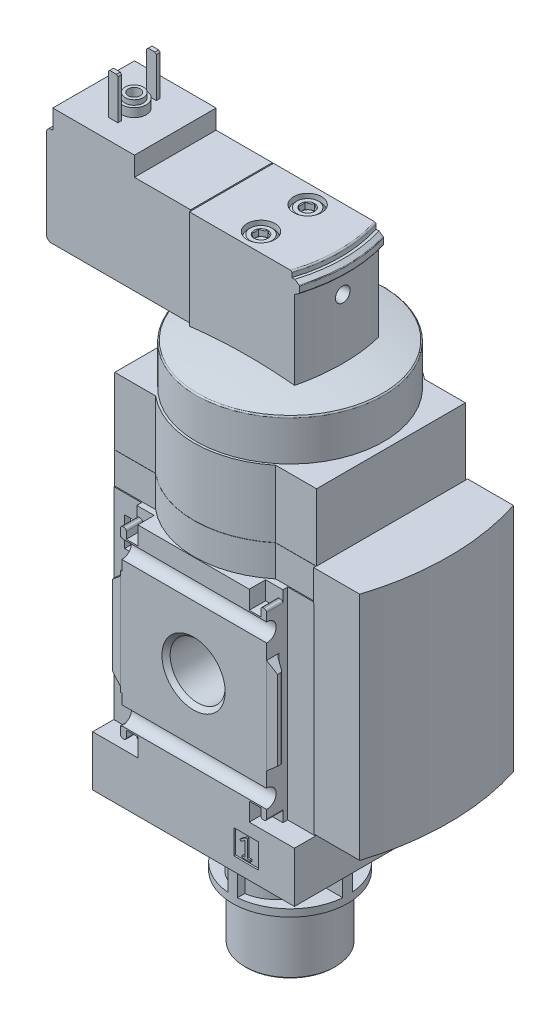
SolidWorks part; units mm, degrees
ref_plane "Front Plane" through (0, 0, 0) normal (0, 0, 1) x (1, 0, 0)
ref_plane "Top Plane" through (0, 0, 0) normal (0, 1, 0) x (1, 0, 0)
ref_plane "Right Plane" through (0, 0, 0) normal (1, 0, 0) x (0, 0, -1)
ref_plane "Plane1" through (0, -8, 0) normal (0, 1, 0) x (1, 0, 0)
sketch "Sketch1" plane through (0, -8, 0) normal (0, 1, 0) x (1, 0, 0)
  line L0 (-21, -15.5) -> (-12.5, -15.5)
  line L1 (12.5, -15.5) -> (21, -15.5)
  line L2 (21, -15.5) -> (21, 15.5)
  line L3 (21, 15.5) -> (12.5, 15.5)
  line L4 (-12.5, 15.5) -> (-21, 15.5)
  line L5 (-21, 15.5) -> (-21, -15.5)
  arc A0 (-12.5, -15.5) -> (12.5, -15.5) centre (0, -0.3889) ccw
  arc A1 (12.5, 15.5) -> (-12.5, 15.5) centre (0, 0.3889) ccw
extrude "Boss-Extrude1" add sketch "Sketch1" along normal blind 49.5
ref_plane "Plane2" through (0, 0, 0) normal (0, 0, 1) x (1, 0, 0)
sketch "Sketch2" plane through (0, 0, 0) normal (0, 0, 1) x (1, 0, 0)
  line L0 (-21, -21) -> (21, -21)
  line L1 (21, -21) -> (21, 21)
  line L2 (21, 21) -> (-21, 21)
  line L3 (-21, 21) -> (-21, -21)
extrude "Boss-Extrude2" add sketch "Sketch2" against normal blind 20.1 and the other way blind 20.1
ref_plane "Plane3" through (0, -31.5, 0) normal (0, 1, 0) x (1, 0, 0)
sketch "Sketch3" plane through (0, -31.5, 0) normal (0, 1, 0) x (1, 0, 0)
  line L0 (-21, -20.1) -> (21, -20.1)
  line L1 (21, -20.1) -> (21, 20.1)
  line L2 (21, 20.1) -> (-21, 20.1)
  line L3 (-21, 20.1) -> (-21, -20.1)
extrude "Boss-Extrude3" add sketch "Sketch3" along normal blind 10.5
ref_plane "Plane4" through (0, 27.5, 0) normal (0, 1, 0) x (1, 0, 0)
sketch "Sketch4" plane through (0, 27.5, 0) normal (0, 1, 0) x (1, 0, 0)
  line L0 (-23, -20) -> (23, -20)
  line L1 (23, -20) -> (23, 20)
  line L2 (23, 20) -> (-23, 20)
  line L3 (-23, 20) -> (-23, -20)
  line L4 (-20.58, -15.19) -> (-12.25, -15.19)
  line L5 (12.25, -15.19) -> (20.58, -15.19)
  line L6 (20.58, -15.19) -> (20.58, 15.19)
  line L7 (20.58, 15.19) -> (12.25, 15.19)
  line L8 (-12.25, 15.19) -> (-20.58, 15.19)
  line L9 (-20.58, 15.19) -> (-20.58, -15.19)
  arc A0 (-12.25, -15.19) -> (12.25, -15.19) centre (0, -0.3811) ccw
  arc A1 (12.25, 15.19) -> (-12.25, 15.19) centre (0, 0.3811) ccw
extrude "Cut-Extrude1" cut sketch "Sketch4" along normal blind 14
ref_plane "Plane5" through (0, 27.54, 0) normal (0, 1, 0) x (1, 0, 0)
sketch "Sketch5" plane through (0, 27.54, 0) normal (0, 1, 0) x (1, 0, 0)
  line L0 (-21, -15.5) -> (-12.5, -15.5)
  line L1 (12.5, -15.5) -> (21, -15.5)
  line L2 (21, -15.5) -> (21, 15.5)
  line L3 (21, 15.5) -> (12.5, 15.5)
  line L4 (-12.5, 15.5) -> (-21, 15.5)
  line L5 (-21, 15.5) -> (-21, -15.5)
  arc A0 (-12.5, -15.5) -> (12.5, -15.5) centre (0, -0.3889) ccw
  arc A1 (12.5, 15.5) -> (-12.5, 15.5) centre (0, 0.3889) ccw
extrude "Boss-Extrude4" add sketch "Sketch5" along normal blind 13.96
ref_plane "Plane6" through (0, 27.5, 0) normal (0, 1, 0) x (1, 0, 0)
sketch "Sketch6" plane through (0, 27.5, 0) normal (0, 1, 0) x (1, 0, 0)
  line L0 (20.9, -16) -> (30.5, -16)
  line L1 (30.5, 16) -> (20.9, 16)
  line L2 (20.9, 16) -> (20.9, -16)
  arc A0 (30.5, -16) -> (30.5, 16) centre (-19.45, 0) ccw
extrude "Boss-Extrude5" add sketch "Sketch6" against normal blind 48
ref_plane "Plane7" through (0, 0, 0) normal (1, 0, 0) x (0, 0, -1)
sketch "Sketch7" plane through (0, 0, 0) normal (1, 0, 0) x (0, 0, -1)
  line L0 (-20.1, 0) -> (-20.1, 6.5785)
  line L1 (-20.1, 6.5785) -> (-19.244, 5.7225)
  line L2 (-19.244, 5.7225) -> (-7.799, 5.7225)
  line L3 (-7.799, 5.7225) -> (-6.943, 6.5785)
  line L4 (-6.943, 6.5785) -> (-6.943, 0)
  line L5 (-6.943, 0) -> (-20.1, 0)
  line L6 (-6.943, 0) -> (-20.1, 0) construction
revolve "Cut-Revolve1" cut sketch "Sketch7" angle 360 about L6 reverse direction yes
cosmetic thread "Cosmetic Thread1" parameters "D1"=13.157, "D2"=13.157
ref_plane "Plane8" through (0, 0, 0) normal (1, 0, 0) x (0, 0, -1)
sketch "Sketch8" plane through (0, 0, 0) normal (1, 0, 0) x (0, 0, -1)
  line L0 (6.943, 0) -> (6.943, 6.5785)
  line L1 (6.943, 6.5785) -> (7.799, 5.7225)
  line L2 (7.799, 5.7225) -> (19.244, 5.7225)
  line L3 (19.244, 5.7225) -> (20.1, 6.5785)
  line L4 (20.1, 6.5785) -> (20.1, 0)
  line L5 (20.1, 0) -> (6.943, 0)
  line L6 (20.1, 0) -> (6.943, 0) construction
revolve "Cut-Revolve2" cut sketch "Sketch8" angle 360 about L6 reverse direction yes
cosmetic thread "Cosmetic Thread2" parameters "D1"=13.157, "D2"=13.157
ref_plane "Plane9" through (0, 0, 20.1) normal (0, 0, 1) x (1, 0, 0)
sketch "Sketch9" plane through (0, 0, 20.1) normal (0, 0, 1) x (1, 0, 0)
  line L0 (8.4, -23.59) -> (8.4, -28.69)
  line L1 (8.4, -28.69) -> (13.5, -28.69)
  line L2 (13.5, -28.69) -> (13.5, -23.59)
  line L3 (13.5, -23.59) -> (8.4, -23.59)
  line L4 (9.6632, -25.02) -> (9.7613, -25.2755)
  line L5 (9.7613, -25.2755) -> (10.24, -25.0624)
  line L6 (10.24, -25.0624) -> (10.71, -24.78)
  line L7 (10.71, -24.78) -> (10.71, -27.76)
  line L8 (10.71, -27.76) -> (10.1, -27.76)
  line L9 (10.1, -27.76) -> (10.1, -28.14)
  line L10 (10.1, -28.14) -> (11.8, -28.14)
  line L11 (11.8, -28.14) -> (11.8, -27.76)
  line L12 (11.8, -27.76) -> (11.19, -27.76)
  line L13 (11.19, -27.76) -> (11.19, -24.21)
  line L14 (11.19, -24.21) -> (10.82, -24.21)
  line L15 (10.82, -24.21) -> (9.6632, -25.02)
extrude "Cut-Extrude2" cut sketch "Sketch9" against normal blind 0.35
ref_plane "Plane10" through (0, 0, -20.1) normal (0, 0, 1) x (1, 0, 0)
sketch "Sketch10" plane through (0, 0, -20.1) normal (0, 0, 1) x (1, 0, 0)
  line L0 (-13.5, -23.59) -> (-13.5, -28.69)
  line L1 (-13.5, -28.69) -> (-8.4, -28.69)
  line L2 (-8.4, -28.69) -> (-8.4, -23.59)
  line L3 (-8.4, -23.59) -> (-13.5, -23.59)
  line L4 (-12.0398, -25.2415) -> (-10.4706, -27.4826)
  line L5 (-10.5525, -27.64) -> (-12.15, -27.64)
  line L6 (-12.15, -27.64) -> (-12.15, -28.14)
  line L7 (-12.15, -28.14) -> (-9.75, -28.14)
  line L8 (-9.75, -28.14) -> (-9.75, -27.64)
  line L9 (-9.75, -27.64) -> (-11.5752, -25.0334)
  line L10 (-11.3704, -24.64) -> (-10.75, -24.64)
  line L11 (-10.25, -25.14) -> (-9.75, -25.14)
  line L12 (-10.75, -24.14) -> (-11.4664, -24.14)
  arc A0 (-11.4664, -24.14) -> (-12.0398, -25.2415) centre (-11.4664, -24.84) ccw
  arc A1 (-10.4706, -27.4826) -> (-10.5525, -27.64) centre (-10.5525, -27.54) cw
  arc A2 (-11.5752, -25.0334) -> (-11.3704, -24.64) centre (-11.3704, -24.89) cw
  arc A3 (-10.75, -24.64) -> (-10.25, -25.14) centre (-10.75, -25.14) cw
  arc A4 (-9.75, -25.14) -> (-10.75, -24.14) centre (-10.75, -25.14) ccw
extrude "Cut-Extrude3" cut sketch "Sketch10" along normal blind 0.35
ref_plane "Plane11" through (0, 0, 0) normal (1, 0, 0) x (0, 0, -1)
sketch "Sketch11" plane through (0, 0, 0) normal (1, 0, 0) x (0, 0, -1)
  line L0 (21.9, -15) -> (21.9, 15)
  line L1 (20.5, 13.167) -> (20.5, -13.167)
  arc A0 (20.5, -13.167) -> (21.9, -15) centre (20, -15) ccw
  arc A1 (21.9, 15) -> (20.5, 13.167) centre (20, 15) ccw
extrude "Cut-Extrude4" cut sketch "Sketch11" against normal blind 25 and the other way blind 25
ref_plane "Plane12" through (0, 0, 0) normal (1, 0, 0) x (0, 0, -1)
sketch "Sketch12" plane through (0, 0, 0) normal (1, 0, 0) x (0, 0, -1)
  line L0 (-21.9, 15) -> (-21.9, -15)
  line L1 (-20.5, -13.167) -> (-20.5, 13.167)
  arc A0 (-21.9, -15) -> (-20.5, -13.167) centre (-20, -15) ccw
  arc A1 (-20.5, 13.167) -> (-21.9, 15) centre (-20, 15) ccw
extrude "Cut-Extrude5" cut sketch "Sketch12" against normal blind 25 and the other way blind 25
ref_plane "Plane13" through (0, 0, 20.1) normal (0, 0, 1) x (1, 0, 0)
sketch "Sketch13" plane through (0, 0, 20.1) normal (0, 0, 1) x (1, 0, 0)
  line L0 (11.6, 21) -> (11.6, 17.2)
  line L1 (11.6, 17.2) -> (14, 17.2)
  line L2 (14, 17.2) -> (14, 18.6)
  line L3 (14.5, 19.1) -> (14.7, 19.1)
  line L4 (15.2, 18.6) -> (15.2, 9.95)
  line L5 (15.2, 9.95) -> (21.5, 4.6637)
  line L6 (21.5, 4.6637) -> (21.5, -4.6637)
  line L7 (21.5, -4.6637) -> (15.2, -9.95)
  line L8 (15.2, -9.95) -> (15.2, -18.6)
  line L9 (14.7, -19.1) -> (14.5, -19.1)
  line L10 (14, -18.6) -> (14, -17.2)
  line L11 (14, -17.2) -> (11.6, -17.2)
  line L12 (11.6, -17.2) -> (11.6, -21)
  line L13 (11.6, -21) -> (22, -21)
  line L14 (22, -21) -> (22, 21)
  line L15 (22, 21) -> (11.6, 21)
  arc A0 (14, 18.6) -> (14.5, 19.1) centre (14.5, 18.6) cw
  arc A1 (14.7, 19.1) -> (15.2, 18.6) centre (14.7, 18.6) cw
  arc A2 (15.2, -18.6) -> (14.7, -19.1) centre (14.7, -18.6) cw
  arc A3 (14.5, -19.1) -> (14, -18.6) centre (14.5, -18.6) cw
extrude "Cut-Extrude6" cut sketch "Sketch13" against normal blind 3.4 and the other way blind 3.4
ref_plane "Plane14" through (0, 0, 20.1) normal (0, 0, 1) x (1, 0, 0)
sketch "Sketch14" plane through (0, 0, 20.1) normal (0, 0, 1) x (1, 0, 0)
  line L0 (-22, -21) -> (-11.6, -21)
  line L1 (-11.6, -21) -> (-11.6, -17.2)
  line L2 (-11.6, -17.2) -> (-14, -17.2)
  line L3 (-14, -17.2) -> (-14, -18.6)
  line L4 (-14.5, -19.1) -> (-14.7, -19.1)
  line L5 (-15.2, -18.6) -> (-15.2, -9.95)
  line L6 (-15.2, -9.95) -> (-21.5, -4.6637)
  line L7 (-21.5, -4.6637) -> (-21.5, 4.6637)
  line L8 (-21.5, 4.6637) -> (-15.2, 9.95)
  line L9 (-15.2, 9.95) -> (-15.2, 18.6)
  line L10 (-14.7, 19.1) -> (-14.5, 19.1)
  line L11 (-14, 18.6) -> (-14, 17.2)
  line L12 (-14, 17.2) -> (-11.6, 17.2)
  line L13 (-11.6, 17.2) -> (-11.6, 21)
  line L14 (-11.6, 21) -> (-22, 21)
  line L15 (-22, 21) -> (-22, -21)
  arc A0 (-14, -18.6) -> (-14.5, -19.1) centre (-14.5, -18.6) cw
  arc A1 (-14.7, -19.1) -> (-15.2, -18.6) centre (-14.7, -18.6) cw
  arc A2 (-15.2, 18.6) -> (-14.7, 19.1) centre (-14.7, 18.6) cw
  arc A3 (-14.5, 19.1) -> (-14, 18.6) centre (-14.5, 18.6) cw
extrude "Cut-Extrude7" cut sketch "Sketch14" against normal blind 3.4 and the other way blind 3.4
ref_plane "Plane15" through (0, 0, -20.1) normal (0, 0, 1) x (1, 0, 0)
sketch "Sketch15" plane through (0, 0, -20.1) normal (0, 0, 1) x (1, 0, 0)
  line L0 (11.6, 21) -> (11.6, 17.2)
  line L1 (11.6, 17.2) -> (14, 17.2)
  line L2 (14, 17.2) -> (14, 18.6)
  line L3 (14.5, 19.1) -> (14.7, 19.1)
  line L4 (15.2, 18.6) -> (15.2, 9.95)
  line L5 (15.2, 9.95) -> (21.5, 4.6637)
  line L6 (21.5, 4.6637) -> (21.5, -4.6637)
  line L7 (21.5, -4.6637) -> (15.2, -9.95)
  line L8 (15.2, -9.95) -> (15.2, -18.6)
  line L9 (14.7, -19.1) -> (14.5, -19.1)
  line L10 (14, -18.6) -> (14, -17.2)
  line L11 (14, -17.2) -> (11.6, -17.2)
  line L12 (11.6, -17.2) -> (11.6, -21)
  line L13 (11.6, -21) -> (22, -21)
  line L14 (22, -21) -> (22, 21)
  line L15 (22, 21) -> (11.6, 21)
  arc A0 (14, 18.6) -> (14.5, 19.1) centre (14.5, 18.6) cw
  arc A1 (14.7, 19.1) -> (15.2, 18.6) centre (14.7, 18.6) cw
  arc A2 (15.2, -18.6) -> (14.7, -19.1) centre (14.7, -18.6) cw
  arc A3 (14.5, -19.1) -> (14, -18.6) centre (14.5, -18.6) cw
extrude "Cut-Extrude8" cut sketch "Sketch15" against normal blind 3.4 and the other way blind 3.4
ref_plane "Plane16" through (0, 0, -20.1) normal (0, 0, 1) x (1, 0, 0)
sketch "Sketch16" plane through (0, 0, -20.1) normal (0, 0, 1) x (1, 0, 0)
  line L0 (-22, -21) -> (-11.6, -21)
  line L1 (-11.6, -21) -> (-11.6, -17.2)
  line L2 (-11.6, -17.2) -> (-14, -17.2)
  line L3 (-14, -17.2) -> (-14, -18.6)
  line L4 (-14.5, -19.1) -> (-14.7, -19.1)
  line L5 (-15.2, -18.6) -> (-15.2, -9.95)
  line L6 (-15.2, -9.95) -> (-21.5, -4.6637)
  line L7 (-21.5, -4.6637) -> (-21.5, 4.6637)
  line L8 (-21.5, 4.6637) -> (-15.2, 9.95)
  line L9 (-15.2, 9.95) -> (-15.2, 18.6)
  line L10 (-14.7, 19.1) -> (-14.5, 19.1)
  line L11 (-14, 18.6) -> (-14, 17.2)
  line L12 (-14, 17.2) -> (-11.6, 17.2)
  line L13 (-11.6, 17.2) -> (-11.6, 21)
  line L14 (-11.6, 21) -> (-22, 21)
  line L15 (-22, 21) -> (-22, -21)
  arc A0 (-14, -18.6) -> (-14.5, -19.1) centre (-14.5, -18.6) cw
  arc A1 (-14.7, -19.1) -> (-15.2, -18.6) centre (-14.7, -18.6) cw
  arc A2 (-15.2, 18.6) -> (-14.7, 19.1) centre (-14.7, 18.6) cw
  arc A3 (-14.5, 19.1) -> (-14, 18.6) centre (-14.5, 18.6) cw
extrude "Cut-Extrude9" cut sketch "Sketch16" against normal blind 3.4 and the other way blind 3.4
ref_plane "Plane17" through (0, 0, 0) normal (0, 1, 0) x (1, 0, 0)
sketch "Sketch17" plane through (0, 0, 0) normal (0, 1, 0) x (1, 0, 0)
  line L0 (-21, 25.1) -> (-21, 15.7)
  line L1 (-21, 15.7) -> (-15.2, 15.7)
  line L2 (-15.2, 15.7) -> (-15.2, 17.4001)
  line L3 (-15.6493, 18.1191) -> (-16.9192, 18.7385)
  line L4 (-17.2, 19.1879) -> (-17.2, 19.8)
  line L5 (-17.2, 19.8) -> (-15.2, 20.1)
  line L6 (-15.2, 20.1) -> (15.2, 20.1)
  line L7 (15.2, 20.1) -> (17.2, 19.8)
  line L8 (17.2, 19.8) -> (17.2, 19.1879)
  line L9 (16.9192, 18.7385) -> (15.6493, 18.1191)
  line L10 (15.2, 17.4001) -> (15.2, 15.7)
  line L11 (15.2, 15.7) -> (21, 15.7)
  line L12 (21, 15.7) -> (21, 25.1)
  line L13 (21, 25.1) -> (-21, 25.1)
  arc A0 (-15.2, 17.4001) -> (-15.6493, 18.1191) centre (-16, 17.4001) ccw
  arc A1 (-16.9192, 18.7385) -> (-17.2, 19.1879) centre (-16.7, 19.1879) cw
  arc A2 (17.2, 19.1879) -> (16.9192, 18.7385) centre (16.7, 19.1879) cw
  arc A3 (15.6493, 18.1191) -> (15.2, 17.4001) centre (16, 17.4001) ccw
extrude "Cut-Extrude10" cut sketch "Sketch17" against normal blind 21 and the other way blind 21
ref_plane "Plane18" through (0, 0, 0) normal (0, 1, 0) x (1, 0, 0)
sketch "Sketch18" plane through (0, 0, 0) normal (0, 1, 0) x (1, 0, 0)
  line L0 (-21, -25.1) -> (21, -25.1)
  line L1 (21, -25.1) -> (21, -15.7)
  line L2 (21, -15.7) -> (15.2, -15.7)
  line L3 (15.2, -15.7) -> (15.2, -17.4001)
  line L4 (15.6493, -18.1191) -> (16.9192, -18.7385)
  line L5 (17.2, -19.1879) -> (17.2, -19.8)
  line L6 (17.2, -19.8) -> (15.2, -20.1)
  line L7 (15.2, -20.1) -> (-15.2, -20.1)
  line L8 (-15.2, -20.1) -> (-17.2, -19.8)
  line L9 (-17.2, -19.8) -> (-17.2, -19.1879)
  line L10 (-16.9192, -18.7385) -> (-15.6493, -18.1191)
  line L11 (-15.2, -17.4001) -> (-15.2, -15.7)
  line L12 (-15.2, -15.7) -> (-21, -15.7)
  line L13 (-21, -15.7) -> (-21, -25.1)
  arc A0 (15.2, -17.4001) -> (15.6493, -18.1191) centre (16, -17.4001) ccw
  arc A1 (16.9192, -18.7385) -> (17.2, -19.1879) centre (16.7, -19.1879) cw
  arc A2 (-17.2, -19.1879) -> (-16.9192, -18.7385) centre (-16.7, -19.1879) cw
  arc A3 (-15.6493, -18.1191) -> (-15.2, -17.4001) centre (-16, -17.4001) ccw
extrude "Cut-Extrude11" cut sketch "Sketch18" against normal blind 21 and the other way blind 21
ref_plane "Plane19" through (0, 40, 0) normal (0, 1, 0) x (1, 0, 0)
sketch "Sketch19" plane through (0, 40, 0) normal (0, 1, 0) x (1, 0, 0)
  line L0 (-2, -2) -> (2, -2)
  line L1 (2, -2) -> (2, 2)
  line L2 (2, 2) -> (-2, 2)
  line L3 (-2, 2) -> (-2, -2)
extrude "Boss-Extrude6" add sketch "Sketch19" along normal blind 15
ref_plane "Plane20" through (0, 0, 0) normal (0, 0, 1) x (1, 0, 0)
sketch "Sketch20" plane through (0, 0, 0) normal (0, 0, 1) x (1, 0, 0)
  line L0 (-42.2, 70.7) -> (-42.2, 52.2)
  line L1 (-41.2, 51.2) -> (-12.2, 51.2)
  line L2 (-12.2, 51.2) -> (-12.2, 49.95)
  line L3 (-12.2, 49.95) -> (11, 49.95)
  line L4 (11, 49.95) -> (11, 71.45)
  line L5 (11, 71.45) -> (-12.2, 71.45)
  line L6 (-12.2, 71.45) -> (-12.2, 71.7)
  line L7 (-12.2, 71.7) -> (-23.9, 71.7)
  line L8 (-23.9, 71.7) -> (-23.9, 75.7)
  line L9 (-23.9, 75.7) -> (-40.9, 75.7)
  line L10 (-40.9, 75.7) -> (-40.9, 71.7)
  line L11 (-40.9, 71.7) -> (-41.2, 71.7)
  arc A0 (-42.2, 52.2) -> (-41.2, 51.2) centre (-41.2, 52.2) ccw
  arc A1 (-41.2, 71.7) -> (-42.2, 70.7) centre (-41.2, 70.7) ccw
extrude "Boss-Extrude7" add sketch "Sketch20" against normal blind 8.75 and the other way blind 8.75
ref_plane "Plane21" through (0, 51.2, 0) normal (0, 1, 0) x (1, 0, 0)
sketch "Sketch21" plane through (0, 51.2, 0) normal (0, 1, 0) x (1, 0, 0)
  line L0 (-52.2, 18.5) -> (-52.2, -18.5)
  line L1 (-52.2, -18.5) -> (-12.2, -18.5)
  line L2 (-12.2, -18.5) -> (-12.2, -8.5)
  line L3 (-12.2, -8.5) -> (-42.2, -8.5)
  line L4 (-42.2, -8.5) -> (-42.2, 8.5)
  line L5 (-42.2, 8.5) -> (-12.2, 8.5)
  line L6 (-12.2, 8.5) -> (-12.2, 18.5)
  line L7 (-12.2, 18.5) -> (-52.2, 18.5)
extrude "Cut-Extrude12" cut sketch "Sketch21" along normal blind 25
ref_plane "Plane22" through (0, 0, 0) normal (0, 0, 1) x (1, 0, 0)
sketch "Sketch22" plane through (0, 0, 0) normal (0, 0, 1) x (1, 0, 0)
  line L0 (11, 50.7) -> (14, 50.7)
  line L1 (14, 50.7) -> (14, 71.7)
  line L2 (14, 71.7) -> (11, 71.7)
  line L3 (11, 71.7) -> (11, 50.7)
  line L4 (-19, 50.7) -> (-19, 71.7) construction
revolve "Cut-Revolve3" cut sketch "Sketch22" angle 20 about L4 other way angle 20 reverse direction yes
ref_plane "Plane23" through (0, 0, 0) normal (0, 0, 1) x (1, 0, 0)
sketch "Sketch23" plane through (0, 0, 0) normal (0, 0, 1) x (1, 0, 0)
  line L0 (9, 70.3) -> (9, 67.5)
  line L1 (9, 67.5) -> (11, 67.5)
  line L2 (11, 67.5) -> (11.9147, 68.1405)
  line L3 (12, 68.3043) -> (12, 69.4957)
  line L4 (11.9147, 69.6595) -> (11, 70.3)
  line L5 (11, 70.3) -> (9, 70.3)
  line L6 (-18.5, 68.3043) -> (-18.5, 69.4957) construction
  arc A0 (11.9147, 68.1405) -> (12, 68.3043) centre (11.8, 68.3043) ccw
  arc A1 (12, 69.4957) -> (11.9147, 69.6595) centre (11.8, 69.4957) ccw
revolve "Revolve1" add sketch "Sketch23" angle 20 about L6 other way angle 20 reverse direction yes
ref_plane "Plane24" through (0, 70.7, 0) normal (0, 1, 0) x (1, 0, 0)
sketch "Sketch24" plane through (0, 70.7, 0) normal (0, 1, 0) x (1, 0, 0)
  line L0 (-3, -13.75) -> (22, -13.75)
  line L1 (22, -13.75) -> (22, 13.75)
  line L2 (22, 13.75) -> (-3, 13.75)
  line L3 (-3, 13.75) -> (-3, 8.75)
  line L4 (-3, 8.75) -> (17, 8.75)
  line L5 (17, 8.75) -> (17, -8.75)
  line L6 (17, -8.75) -> (-3, -8.75)
  line L7 (-3, -8.75) -> (-3, -13.75)
extrude "Cut-Extrude13" cut sketch "Sketch24" against normal blind 5
ref_plane "Plane25" through (0, 0, 0) normal (0, 0, 1) x (1, 0, 0)
sketch "Sketch25" plane through (0, 0, 0) normal (0, 0, 1) x (1, 0, 0)
  line L0 (19.5, 49.7935) -> (19.5, 41.5)
  line L1 (19.5, 41.5) -> (0, 41.5)
  line L2 (0, 41.5) -> (0, 51.9597)
  line L3 (0, 41.5) -> (0, 51.9597) construction
  arc A0 (0, 51.9597) -> (19.2578, 50.0878) centre (0, -48.0403) cw
  arc A1 (19.2578, 50.0878) -> (19.5, 49.7935) centre (19.2, 49.7935) cw
revolve "Revolve2" add sketch "Sketch25" angle 360 about L3 reverse direction yes
ref_plane "Plane26" through (0, 0, 0) normal (0, 0, 1) x (1, 0, 0)
sketch "Sketch26" plane through (0, 0, 0) normal (0, 0, 1) x (1, 0, 0)
  line L0 (11, 63.8) -> (11, 62.2684)
  line L1 (11, 62.2684) -> (6, 63.15)
  line L2 (6, 63.15) -> (6, 63.8)
  line L3 (6, 63.8) -> (11, 63.8)
  line L4 (6, 63.8) -> (11, 63.8) construction
revolve "Cut-Revolve4" cut sketch "Sketch26" angle 360 about L4 reverse direction yes
ref_plane "Plane27" through (0, 0, 0) normal (0, 0, 1) x (1, 0, 0)
sketch "Sketch27" plane through (0, 0, 0) normal (0, 0, 1) x (1, 0, 0)
  line L0 (10.5, 71.15) -> (10.5, 70.25)
  line L1 (10.5, 70.25) -> (15.5, 70.25)
  line L2 (15.5, 70.25) -> (15.5, 71.45)
  line L3 (15.5, 71.45) -> (10.2, 71.45)
  line L4 (-18, 70.25) -> (-18, 71.45) construction
  arc A0 (10.2, 71.45) -> (10.5, 71.15) centre (10.2, 71.15) cw
revolve "Cut-Revolve5" cut sketch "Sketch27" angle 20 about L4 other way angle 20 reverse direction yes
ref_plane "Plane28" through (0, 0, 4) normal (0, 0, 1) x (1, 0, 0)
sketch "Sketch28" plane through (0, 0, 4) normal (0, 0, 1) x (1, 0, 0)
  line L0 (-33.45, 84) -> (-33.45, 75.7)
  line L1 (-33.45, 75.7) -> (-31.45, 75.7)
  line L2 (-31.45, 75.7) -> (-31.45, 84)
  line L3 (-31.45, 84) -> (-31.75, 84.3)
  line L4 (-31.75, 84.3) -> (-33.15, 84.3)
  line L5 (-33.15, 84.3) -> (-33.45, 84)
extrude "Boss-Extrude8" add sketch "Sketch28" against normal blind 0.4 and the other way blind 0.4
ref_plane "Plane29" through (0, 0, -4) normal (0, 0, 1) x (1, 0, 0)
sketch "Sketch29" plane through (0, 0, -4) normal (0, 0, 1) x (1, 0, 0)
  line L0 (-33.45, 84) -> (-33.45, 75.7)
  line L1 (-33.45, 75.7) -> (-31.45, 75.7)
  line L2 (-31.45, 75.7) -> (-31.45, 84)
  line L3 (-31.45, 84) -> (-31.75, 84.3)
  line L4 (-31.75, 84.3) -> (-33.15, 84.3)
  line L5 (-33.15, 84.3) -> (-33.45, 84)
extrude "Boss-Extrude9" add sketch "Sketch29" against normal blind 0.4 and the other way blind 0.4
ref_plane "Plane30" through (0, 0, 0) normal (0, 0, 1) x (1, 0, 0)
sketch "Sketch30" plane through (0, 0, 0) normal (0, 0, 1) x (1, 0, 0)
  line L0 (-32.45, 78.5) -> (-30.55, 78.5)
  line L1 (-30.55, 78.5) -> (-30.55, 77.5)
  line L2 (-30.55, 77.5) -> (-29.95, 77.5)
  line L3 (-29.95, 77.5) -> (-29.95, 75.7)
  line L4 (-29.95, 75.7) -> (-32.45, 75.7)
  line L5 (-32.45, 75.7) -> (-32.45, 78.5)
  line L6 (-32.45, 75.7) -> (-32.45, 78.5) construction
revolve "Revolve3" add sketch "Sketch30" angle 360 about L6 reverse direction yes
ref_plane "Plane31" through (0, 0, 0) normal (0, 0, 1) x (1, 0, 0)
sketch "Sketch31" plane through (0, 0, 0) normal (0, 0, 1) x (1, 0, 0)
  line L0 (-32.45, 78.5) -> (-31.2, 78.5)
  line L1 (-31.2, 78.5) -> (-31.2, 76)
  line L2 (-31.2, 76) -> (-31.4435, 75.7565)
  line L3 (-31.4435, 75.7565) -> (-31.4435, 72.9)
  line L4 (-31.4435, 72.9) -> (-32.45, 72.9)
  line L5 (-32.45, 72.9) -> (-32.45, 78.5)
  line L6 (-32.45, 72.9) -> (-32.45, 78.5) construction
revolve "Cut-Revolve6" cut sketch "Sketch31" angle 360 about L6 reverse direction yes
cosmetic thread "Cosmetic Thread3" parameters "D1"=3.1, "D2"=2.5
ref_plane "Plane32" through (-1.2, 0, 0) normal (1, 0, 0) x (0, 0, -1)
sketch "Sketch32" plane through (-1.2, 0, 0) normal (1, 0, 0) x (0, 0, -1)
  line L0 (4.85, 71.45) -> (7.75, 71.45)
  line L1 (7.75, 71.45) -> (7.75, 67.95)
  line L2 (7.75, 67.95) -> (7.6, 67.95)
  line L3 (7.6, 67.95) -> (7.6, 70.45)
  line L4 (7.6, 70.45) -> (7.1, 70.95)
  line L5 (7.1, 70.95) -> (6.2934, 70.95)
  line L6 (6.2934, 70.95) -> (6.1, 70.7566)
  line L7 (6.1, 70.7566) -> (6.1, 69.65)
  line L8 (6.1, 69.65) -> (4.85, 68.9283)
  line L9 (4.85, 68.9283) -> (4.85, 71.45)
  line L10 (4.85, 68.9283) -> (4.85, 71.45) construction
revolve "Cut-Revolve7" cut sketch "Sketch32" angle 360 about L10 reverse direction yes
ref_plane "Plane33" through (-1.2, 0, 0) normal (1, 0, 0) x (0, 0, -1)
sketch "Sketch33" plane through (-1.2, 0, 0) normal (1, 0, 0) x (0, 0, -1)
  line L0 (-4.85, 71.45) -> (-1.95, 71.45)
  line L1 (-1.95, 71.45) -> (-1.95, 67.95)
  line L2 (-1.95, 67.95) -> (-2.1, 67.95)
  line L3 (-2.1, 67.95) -> (-2.1, 70.45)
  line L4 (-2.1, 70.45) -> (-2.6, 70.95)
  line L5 (-2.6, 70.95) -> (-3.4066, 70.95)
  line L6 (-3.4066, 70.95) -> (-3.6, 70.7566)
  line L7 (-3.6, 70.7566) -> (-3.6, 69.65)
  line L8 (-3.6, 69.65) -> (-4.85, 68.9283)
  line L9 (-4.85, 68.9283) -> (-4.85, 71.45)
  line L10 (-4.85, 68.9283) -> (-4.85, 71.45) construction
revolve "Cut-Revolve8" cut sketch "Sketch33" angle 360 about L10 reverse direction yes
ref_plane "Plane34" through (0, 70.95, 0) normal (0, 1, 0) x (1, 0, 0)
sketch "Sketch34" plane through (0, 70.95, 0) normal (0, 1, 0) x (1, 0, 0)
  line L0 (-2.45, 4.1283) -> (-1.2, 3.4066)
  line L1 (-1.2, 3.4066) -> (0.05, 4.1283)
  line L2 (0.05, 4.1283) -> (0.05, 5.5717)
  line L3 (0.05, 5.5717) -> (-1.2, 6.2934)
  line L4 (-1.2, 6.2934) -> (-2.45, 5.5717)
  line L5 (-2.45, 5.5717) -> (-2.45, 4.1283)
extrude "Cut-Extrude14" cut sketch "Sketch34" against normal blind 1.3
ref_plane "Plane35" through (0, 70.95, 0) normal (0, 1, 0) x (1, 0, 0)
sketch "Sketch35" plane through (0, 70.95, 0) normal (0, 1, 0) x (1, 0, 0)
  line L0 (-2.45, -5.5717) -> (-1.2, -6.2934)
  line L1 (-1.2, -6.2934) -> (0.05, -5.5717)
  line L2 (0.05, -5.5717) -> (0.05, -4.1283)
  line L3 (0.05, -4.1283) -> (-1.2, -3.4066)
  line L4 (-1.2, -3.4066) -> (-2.45, -4.1283)
  line L5 (-2.45, -4.1283) -> (-2.45, -5.5717)
extrude "Cut-Extrude15" cut sketch "Sketch35" against normal blind 1.3
ref_plane "Plane36" through (0, 0, 0) normal (0, 0, 1) x (1, 0, 0)
sketch "Sketch36" plane through (0, 0, 0) normal (0, 0, 1) x (1, 0, 0)
  line L0 (0, -31.5) -> (14.7, -31.5)
  line L1 (14.7, -31.5) -> (14.7, -32.7)
  line L2 (14.7, -32.7) -> (8.5, -36.2796)
  line L3 (8.5, -36.2796) -> (8.5, -44)
  line L4 (8.5, -44) -> (12, -44)
  line L5 (12, -44) -> (12, -45.5)
  line L6 (12, -45.5) -> (9.425, -46.19)
  line L7 (9.425, -46.19) -> (9.425, -58.2)
  line L8 (9.425, -58.2) -> (9.125, -58.5)
  line L9 (9.125, -58.5) -> (0, -58.5)
  line L10 (0, -58.5) -> (0, -31.5)
  line L11 (0, -58.5) -> (0, -31.5) construction
revolve "Revolve4" add sketch "Sketch36" angle 360 about L11 reverse direction yes
ref_plane "Plane37" through (0, -44, 0) normal (0, 1, 0) x (1, 0, 0)
sketch "Sketch37" plane through (0, -44, 0) normal (0, 1, 0) x (1, 0, 0)
  line L0 (-11.9583, -1) -> (-7.2284, -1)
  line L1 (-1, -10.433) -> (-1, -11.9583)
  line L2 (1, -11.9583) -> (1, -10.433)
  line L3 (7.2284, -1) -> (11.9583, -1)
  line L4 (11.9583, 1) -> (1, 1)
  line L5 (1, 1) -> (1, 11.9583)
  line L6 (-1, 11.9583) -> (-1, 1)
  line L7 (-1, 1) -> (-11.9583, 1)
  arc A0 (-11.9583, 1) -> (-11.9583, -1) centre (0, 0) ccw
  arc A1 (-7.2284, -1) -> (-1, -10.433) centre (0, -3) ccw
  arc A2 (-1, -11.9583) -> (1, -11.9583) centre (0, 0) ccw
  arc A3 (1, -10.433) -> (7.2284, -1) centre (0, -3) ccw
  arc A4 (11.9583, -1) -> (11.9583, 1) centre (0, 0) ccw
  arc A5 (1, 11.9583) -> (-1, 11.9583) centre (0, 0) ccw
extrude "Boss-Extrude10" add sketch "Sketch37" along normal blind 14
ref_plane "Plane38" through (0, 0, 0) normal (0, 0, 1) x (1, 0, 0)
sketch "Sketch38" plane through (0, 0, 0) normal (0, 0, 1) x (1, 0, 0)
  line L0 (0, -45.5) -> (5.7225, -45.5)
  line L1 (5.7225, -45.5) -> (5.7225, -57.644)
  line L2 (5.7225, -57.644) -> (6.5785, -58.5)
  line L3 (6.5785, -58.5) -> (6.5785, -59.5)
  line L4 (6.5785, -59.5) -> (0, -59.5)
  line L5 (0, -59.5) -> (0, -45.5)
  line L6 (0, -59.5) -> (0, -45.5) construction
revolve "Cut-Revolve9" cut sketch "Sketch38" angle 360 about L6 reverse direction yes
cosmetic thread "Cosmetic Thread4" parameters "D1"=13, "D2"=13.157
ref_plane "Plane39" through (0, 0, 0) normal (0, 0, 1) x (1, 0, 0)
sketch "Sketch39" plane through (0, 0, 0) normal (0, 0, 1) x (1, 0, 0)
  line L0 (-18.73, 10.97) -> (-14.92, 10.97)
  line L1 (-14.92, 10.97) -> (-14.92, 17.04)
  line L2 (-14.92, 17.04) -> (-18.73, 17.04)
  line L3 (-18.73, 17.04) -> (-18.73, 10.97)
extrude "Cut-Extrude16" cut sketch "Sketch39" against normal blind 22 and the other way blind 22
ref_plane "Plane40" through (0, 0, 0) normal (0, 0, 1) x (1, 0, 0)
sketch "Sketch40" plane through (0, 0, 0) normal (0, 0, 1) x (1, 0, 0)
  line L0 (-18.73, -17.03) -> (-14.92, -17.03)
  line L1 (-14.92, -17.03) -> (-14.92, -10.96)
  line L2 (-14.92, -10.96) -> (-18.73, -10.96)
  line L3 (-18.73, -10.96) -> (-18.73, -17.03)
extrude "Cut-Extrude17" cut sketch "Sketch40" against normal blind 22 and the other way blind 22
ref_plane "Plane41" through (-21, 0, 0) normal (1, 0, 0) x (0, 0, -1)
sketch "Sketch41" plane through (-21, 0, 0) normal (1, 0, 0) x (0, 0, -1)
  line L0 (-14.5, -18.95) -> (14.5, -18.95)
  line L1 (14.5, -18.95) -> (14.5, 18.95)
  line L2 (14.5, 18.95) -> (-14.5, 18.95)
  line L3 (-14.5, 18.95) -> (-14.5, -18.95)
extrude "Cut-Extrude18" cut sketch "Sketch41" against normal blind 11 and the other way blind 11
ref_plane "Plane42" through (0, 0, 0) normal (0, 1, 0) x (1, 0, 0)
sketch "Sketch42" plane through (0, 0, 0) normal (0, 1, 0) x (1, 0, 0)
  line L0 (-11.4891, -14.5) -> (-10, -14.5)
  line L1 (-10, -14.5) -> (-10, 14.5)
  line L2 (-10, 14.5) -> (-11.4891, 14.5)
  arc A0 (-11.4891, 14.5) -> (-11.4891, -14.5) centre (0, 0) ccw
extrude "Boss-Extrude11" add sketch "Sketch42" against normal blind 19 and the other way blind 19
ref_plane "Plane43" through (-19.9, 0, 0) normal (1, 0, 0) x (0, 0, -1)
sketch "Sketch43" plane through (-19.9, 0, 0) normal (1, 0, 0) x (0, 0, -1)
  line L0 (8.8, -21.3) -> (14.6, -21.3)
  line L1 (14.6, -21.3) -> (14.6, -17.1)
  line L2 (14.6, -17.1) -> (13.1633, -17.1)
  line L3 (8.8, -17.5) -> (8.8, -21.3)
  arc A0 (13.1633, -17.1) -> (8.8, -17.5) centre (11, -17.5) ccw
extrude "Boss-Extrude12" add sketch "Sketch43" along normal blind 9
ref_plane "Plane44" through (-19.9, 0, 0) normal (1, 0, 0) x (0, 0, -1)
sketch "Sketch44" plane through (-19.9, 0, 0) normal (1, 0, 0) x (0, 0, -1)
  line L0 (-14.6, 17.1) -> (-13.1633, 17.1)
  line L1 (-8.8, 17.5) -> (-8.8, 21.3)
  line L2 (-8.8, 21.3) -> (-14.6, 21.3)
  line L3 (-14.6, 21.3) -> (-14.6, 17.1)
  arc A0 (-13.1633, 17.1) -> (-8.8, 17.5) centre (-11, 17.5) ccw
extrude "Boss-Extrude13" add sketch "Sketch44" along normal blind 9
ref_plane "Plane45" through (-18, 0, 0) normal (1, 0, 0) x (0, 0, -1)
sketch "Sketch45" plane through (-18, 0, 0) normal (1, 0, 0) x (0, 0, -1)
  circle A0 centre (8.6, 6) radius 3.05
extrude "Boss-Extrude14" add sketch "Sketch45" along normal blind 5
